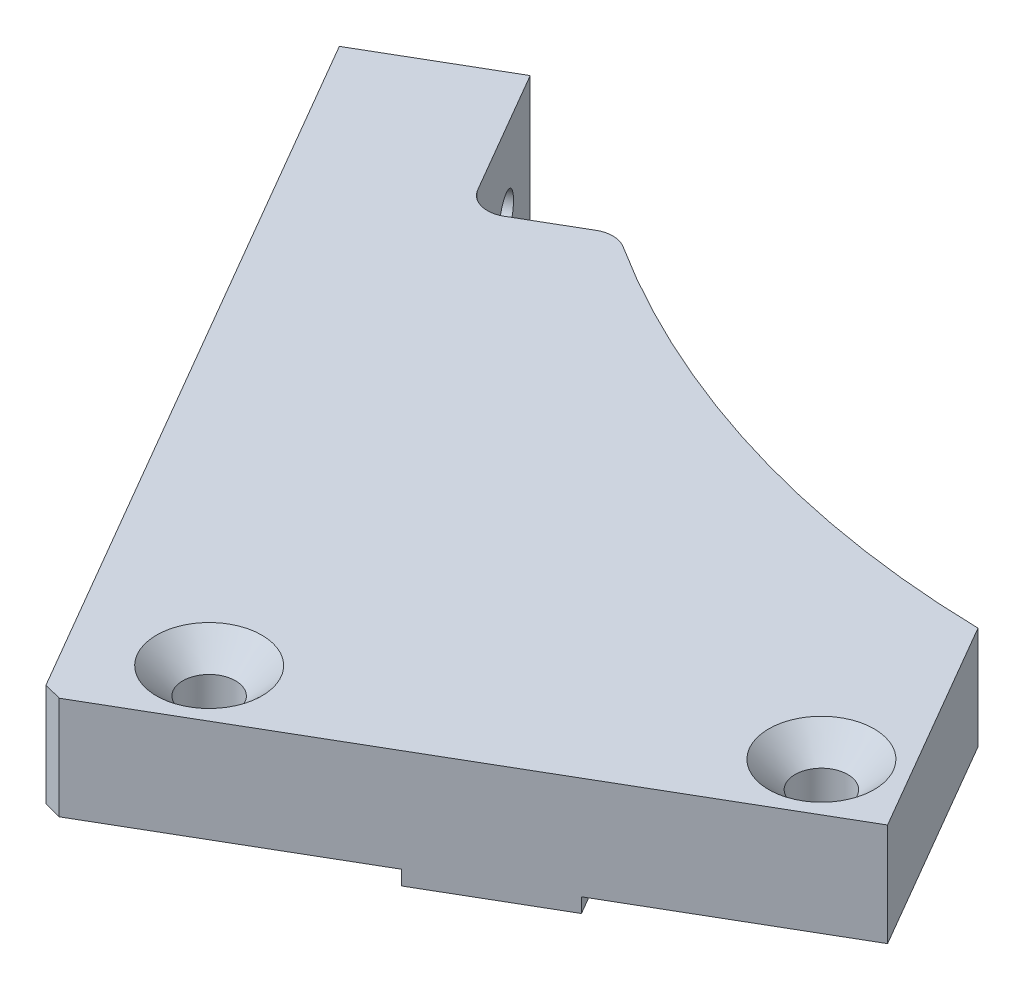
SolidWorks part; units mm, degrees
ref_plane "前视基准面" through (0, 0, 0) normal (0, 0, 1) x (1, 0, 0)
ref_plane "上视基准面" through (0, 0, 0) normal (0, 1, 0) x (1, 0, 0)
ref_plane "右视基准面" through (0, 0, 0) normal (1, 0, 0) x (0, 0, -1)
ref_plane "基准面1" through (0, -3.0728, 0) normal (0, 1, 0) x (1, 0, 0)
sketch "草图1" plane through (0, -3.0728, 0) normal (0, 1, 0) x (1, 0, 0)
  line L0 (-20.0373, -30.7018) -> (-28.2222, -35.456)
  line L1 (-28.2222, -35.456) -> (-15.8079, -56.8287)
  line L2 (-15.8079, -56.8287) -> (4.5128, -45.0255)
  line L3 (4.5128, -45.0255) -> (-0.243, -36.8377)
  arc A0 (-0.243, -36.8377) -> (-20.0373, -30.7018) centre (0.5307, 0.6543) cw
extrude "凸台-拉伸1" add sketch "草图1" against normal blind 3.9
sketch "草图2" plane through (0, -6.9728, 0) normal (0, -1, 0) x (1, 0, 0)
  line L0 (-19.0587, 31.3223) -> (-7.1608, 51.8061)
  line L1 (-7.1608, 51.8061) -> (4.5128, 45.0255)
  line L2 (4.5128, 45.0255) -> (-0.243, 36.8377)
  arc A0 (-0.243, 36.8377) -> (-19.0587, 31.3223) centre (0.5307, -0.6543) ccw
extrude "凸台-拉伸2" add sketch "草图2" along normal blind 0.75
sketch "草图3" plane through (8.2795, 0, 14.2542) normal (-0.5023, 0, -0.8647) x (-0.8647, 0, 0.5023)
  line L0 (42.2125, -6.9728) -> (36.9125, -6.9728)
  line L1 (36.9125, -6.9728) -> (36.9125, -3.0728)
  line L2 (36.9125, -3.0728) -> (42.2125, -3.0728)
  line L3 (42.2125, -3.0728) -> (42.2125, -6.9728)
extrude "凸台-拉伸3" add sketch "草图3" along normal blind 6.5
sketch "草图4" plane through (0, -6.9728, 0) normal (0, -1, 0) x (1, 0, 0)
  line L0 (-26.9039, 27.1734) -> (-31.4869, 29.8354)
  line L1 (-31.4869, 29.8354) -> (-25.4597, 40.2119)
  line L2 (-25.4597, 40.2119) -> (-20.8768, 37.5499)
  line L3 (-20.8768, 37.5499) -> (-26.9039, 27.1734)
extrude "凸台-拉伸4" add sketch "草图4" along normal blind 1
sketch "草图5" plane through (20.6937, 0, 35.6269) normal (0.5023, 0, 0.8647) x (0.8647, 0, -0.5023)
  line L0 (-18.7125, -6.9728) -> (-27.2125, -6.9728)
  line L1 (-27.2125, -6.9728) -> (-27.2125, -7.7228)
  line L2 (-27.2125, -7.7228) -> (-18.7125, -7.7228)
  line L3 (-18.7125, -7.7228) -> (-18.7125, -6.9728)
extrude "切除-拉伸1" cut sketch "草图5" against normal up to next
hole_wizard "Ø1.5 (1.5) 直径孔1" positions "草图7" profile "草图6" hole size "Ø1.5" standard "ANSI Metric"
sketch "草图7" plane through (-31.9187, 0, 18.5399) normal (0.8647, 0, -0.5023) x (-0.5023, 0, -0.8647)
  point P0 (-12.4843, -5.9728)
sketch "草图6" plane through (-25.6483, -5.9728, 29.3352) normal (0, 1, 0) x (-0.5023, 0, -0.8647)
  line L0 (0, 0) -> (0, 18.8578)
  line L1 (0, 18.8578) -> (0.75, 18.8578)
  line L2 (0.75, 18.8578) -> (0.75, 0)
  line L5 (0.75, 0) -> (0, 0)
  line L11 (0, -6.35) -> (0, 107.95) construction
  dimension "通孔孔直径" = 1.5
  dimension "通孔孔深度" = 18.8578
hole_wizard "Ø2.0 (2) 直径孔1" positions "草图9" profile "草图8" hole size "Ø2.0" standard "ANSI Metric"
sketch "草图9" plane through (0, -3.0728, 0) normal (0, 1, 0) x (1, 0, 0)
  point P0 (1.0954, -44.1194)
  point P1 (-13.6048, -52.6579)
sketch "草图8" plane through (1.0954, -3.0728, 44.1194) normal (1, 0, 0) x (0, 0, 1)
  line L0 (0, 0) -> (0, 4.9)
  line L1 (0, 4.9) -> (1, 4.9)
  line L2 (1, 4.9) -> (1, 0)
  line L5 (1, 0) -> (0, 0)
  line L11 (0, -6.35) -> (0, 107.95) construction
  dimension "通孔孔直径" = 2
  dimension "通孔孔深度" = 4.9
chamfer "倒角1" distance 0.75 angle 45 1 edges at (-15.2121, -7.7228, 33.3812)
chamfer "倒角2" distance 1 angle 45 2 edges at (-13.6048, -3.0728, 53.6579) (1.0954, -3.0728, 45.1194)
chamfer "倒角3" distance 0.5 angle 45 1 edges at (-15.8079, -5.0228, 56.8287)
chamfer "倒角4" distance 0.2 angle 45 2 edges at (-12.7257, -7.7228, 42.2253) (-6.715, -7.7228, 42.6186)
fillet "圆角1" radius 1 2 edges at (-20.0373, -5.0228, 30.7018) (-23.6392, -5.0228, 32.794) tangent propagation no
sketch "草图11" plane through (20.6937, 0, 35.6269) normal (0.5023, 0, 0.8647) x (0.8647, 0, -0.5023)
  line L0 (-32.2125, -7.5228) -> (-27.2125, -7.5228)
  line L1 (-32.2125, -7.5228) -> (-32.2125, -6.9728) construction
  line L2 (-27.2125, -7.5228) -> (-27.2125, -7.8929)
  line L3 (-27.2125, -7.8929) -> (-32.2125, -7.8188)
  line L4 (-32.2125, -7.8188) -> (-32.2125, -7.5228)
extrude "切除-拉伸2" cut sketch "草图11" against normal blind 25
